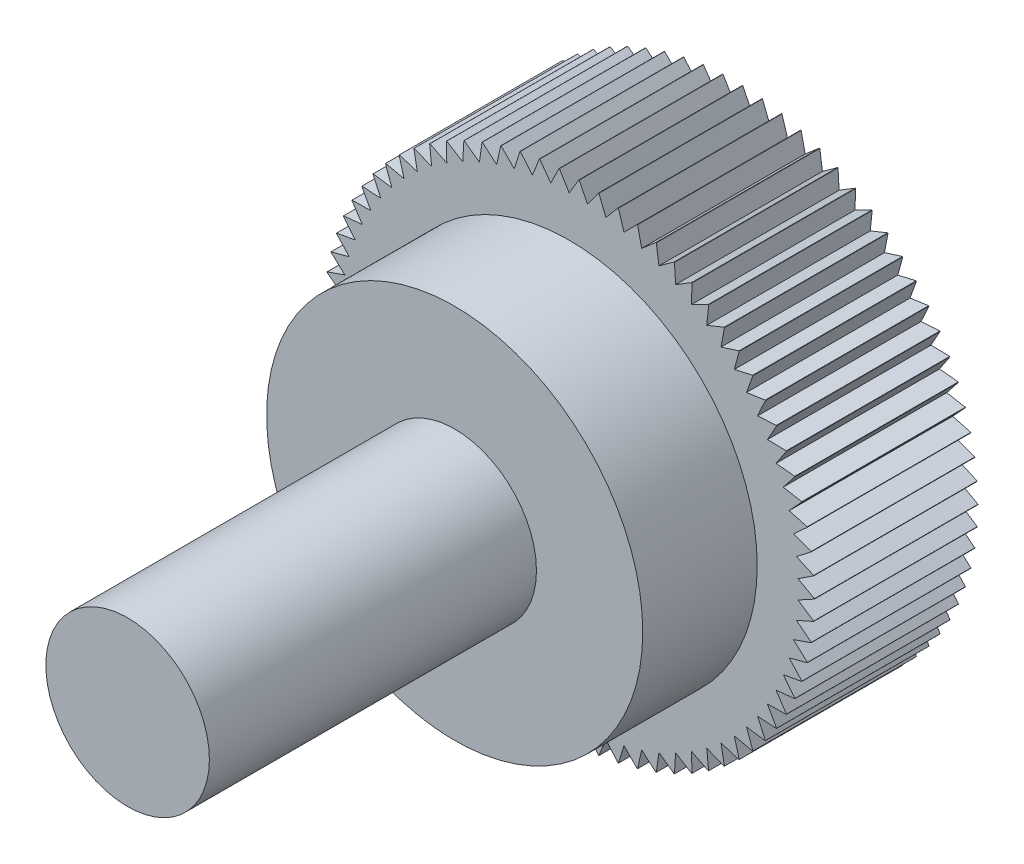
SolidWorks part; units mm, degrees
ref_plane "Front" through (0, 0, 0) normal (0, 0, 1) x (1, 0, 0)
ref_plane "Top" through (0, 0, 0) normal (0, 1, 0) x (1, 0, 0)
ref_plane "Right" through (0, 0, 0) normal (1, 0, 0) x (0, 0, -1)
sketch "Sketch1" plane through (0, 0, 0) normal (0, 0, 1) x (1, 0, 0)
  circle A0 centre (0, 0) radius 7.5
  dimension "D1" = 15
extrude "Extrude1" add sketch "Sketch1" along normal blind 5
sketch "Sketch2" plane through (0, 0, 5) normal (0, 0, 1) x (1, 0, 0)
  circle A0 centre (0, 0) radius 5.75
  dimension "D1" = 11.5
extrude "Extrude2" add sketch "Sketch2" along normal blind 3.5
sketch "Sketch3" plane through (0, 0, 8.5) normal (0, 0, 1) x (1, 0, 0)
  circle A0 centre (0, 0) radius 2.5
  dimension "D1" = 5
extrude "Extrude3" add sketch "Sketch3" along normal blind 10
sketch "Sketch4" plane through (0, 0, 0) normal (0, 0, -1) x (-1, 0, 0)
  line L0 (0, 0) -> (0, 7.5) construction
  line L1 (-0.3, 7.5) -> (0, 7)
  line L2 (0.3, 7.5) -> (0, 7)
  line L3 (-0.3, 7.5) -> (0.3, 7.5)
  line L4 (0.3045, 7.4998) -> (0.5633, 6.9773)
  line L5 (0.9025, 7.4515) -> (0.5633, 6.9773)
  line L6 (0.3045, 7.4998) -> (0.9025, 7.4515)
  line L7 (0.907, 7.451) -> (1.1229, 6.9094)
  line L8 (1.4992, 7.3548) -> (1.1229, 6.9094)
  line L9 (0.907, 7.451) -> (1.4992, 7.3548)
  line L10 (1.5036, 7.3539) -> (1.6752, 6.7966)
  line L11 (2.0862, 7.2103) -> (1.6752, 6.7966)
  line L12 (1.5036, 7.3539) -> (2.0862, 7.2103)
  line L13 (2.0904, 7.209) -> (2.2167, 6.6398)
  line L14 (2.6596, 7.019) -> (2.2167, 6.6398)
  line L15 (2.0904, 7.209) -> (2.6596, 7.019)
  line L16 (2.6638, 7.0174) -> (2.7438, 6.4399)
  line L17 (3.2157, 6.7823) -> (2.7438, 6.4399)
  line L18 (2.6638, 7.0174) -> (3.2157, 6.7823)
  line L19 (3.2198, 6.7803) -> (3.2531, 6.1982)
  line L20 (3.7511, 6.5015) -> (3.2531, 6.1982)
  line L21 (3.2198, 6.7803) -> (3.7511, 6.5015)
  line L22 (3.7549, 6.4993) -> (3.7413, 5.9163)
  line L23 (4.2621, 6.1786) -> (3.7413, 5.9163)
  line L24 (3.7549, 6.4993) -> (4.2621, 6.1786)
  line L25 (4.2657, 6.176) -> (4.2052, 5.5961)
  line L26 (4.7454, 5.8156) -> (4.2052, 5.5961)
  line L27 (4.2657, 6.176) -> (4.7454, 5.8156)
  line L28 (4.7489, 5.8128) -> (4.6419, 5.2396)
  line L29 (5.198, 5.4149) -> (4.6419, 5.2396)
  line L30 (4.7489, 5.8128) -> (5.198, 5.4149)
  line L31 (5.2012, 5.4118) -> (5.0484, 4.8491)
  line L32 (5.6168, 4.9791) -> (5.0484, 4.8491)
  line L33 (5.2012, 5.4118) -> (5.6168, 4.9791)
  line L34 (5.6198, 4.9757) -> (5.4222, 4.4271)
  line L35 (5.9993, 4.511) -> (5.4222, 4.4271)
  line L36 (5.6198, 4.9757) -> (5.9993, 4.511)
  line L37 (6.002, 4.5074) -> (5.7609, 3.9765)
  line L38 (6.3428, 4.0136) -> (5.7609, 3.9765)
  line L39 (6.002, 4.5074) -> (6.3428, 4.0136)
  line L40 (6.3452, 4.0098) -> (6.0622, 3.5)
  line L41 (6.6452, 3.4902) -> (6.0622, 3.5)
  line L42 (6.3452, 4.0098) -> (6.6452, 3.4902)
  line L43 (6.6473, 3.4862) -> (6.3242, 3.0008)
  line L44 (6.9045, 2.9442) -> (6.3242, 3.0008)
  line L45 (6.6473, 3.4862) -> (6.9045, 2.9442)
  line L46 (6.9062, 2.94) -> (6.5451, 2.4822)
  line L47 (7.119, 2.379) -> (6.5451, 2.4822)
  line L48 (6.9062, 2.94) -> (7.119, 2.379)
  line L49 (7.1204, 2.3748) -> (6.7236, 1.9475)
  line L50 (7.2874, 1.7985) -> (6.7236, 1.9475)
  line L51 (7.1204, 2.3748) -> (7.2874, 1.7985)
  line L52 (7.2884, 1.7941) -> (6.8585, 1.4002)
  line L53 (7.4084, 1.2063) -> (6.8585, 1.4002)
  line L54 (7.2884, 1.7941) -> (7.4084, 1.2063)
  line L55 (7.4092, 1.2018) -> (6.949, 0.8438)
  line L56 (7.4815, 0.6062) -> (6.949, 0.8438)
  line L57 (7.4092, 1.2018) -> (7.4815, 0.6062)
  line L58 (7.4818, 0.6018) -> (6.9943, 0.2819)
  line L59 (7.506, 0.0022) -> (6.9943, 0.2819)
  line L60 (7.4818, 0.6018) -> (7.506, 0.0022)
  line L61 (7.506, -0.0022) -> (6.9943, -0.2819)
  line L62 (7.4818, -0.6018) -> (6.9943, -0.2819)
  line L63 (7.506, -0.0022) -> (7.4818, -0.6018)
  line L64 (7.4815, -0.6062) -> (6.949, -0.8438)
  line L65 (7.4092, -1.2018) -> (6.949, -0.8438)
  line L66 (7.4815, -0.6062) -> (7.4092, -1.2018)
  line L67 (7.4084, -1.2063) -> (6.8585, -1.4002)
  line L68 (7.2884, -1.7941) -> (6.8585, -1.4002)
  line L69 (7.4084, -1.2063) -> (7.2884, -1.7941)
  line L70 (7.2874, -1.7985) -> (6.7236, -1.9475)
  line L71 (7.1204, -2.3748) -> (6.7236, -1.9475)
  line L72 (7.2874, -1.7985) -> (7.1204, -2.3748)
  line L73 (7.119, -2.379) -> (6.5451, -2.4822)
  line L74 (6.9062, -2.94) -> (6.5451, -2.4822)
  line L75 (7.119, -2.379) -> (6.9062, -2.94)
  line L76 (6.9045, -2.9442) -> (6.3242, -3.0008)
  line L77 (6.6473, -3.4862) -> (6.3242, -3.0008)
  line L78 (6.9045, -2.9442) -> (6.6473, -3.4862)
  line L79 (6.6452, -3.4902) -> (6.0622, -3.5)
  line L80 (6.3452, -4.0098) -> (6.0622, -3.5)
  line L81 (6.6452, -3.4902) -> (6.3452, -4.0098)
  line L82 (6.3428, -4.0136) -> (5.7609, -3.9765)
  line L83 (6.002, -4.5074) -> (5.7609, -3.9765)
  line L84 (6.3428, -4.0136) -> (6.002, -4.5074)
  line L85 (5.9993, -4.511) -> (5.4222, -4.4271)
  line L86 (5.6198, -4.9757) -> (5.4222, -4.4271)
  line L87 (5.9993, -4.511) -> (5.6198, -4.9757)
  line L88 (5.6168, -4.9791) -> (5.0484, -4.8491)
  line L89 (5.2012, -5.4118) -> (5.0484, -4.8491)
  line L90 (5.6168, -4.9791) -> (5.2012, -5.4118)
  line L91 (5.198, -5.4149) -> (4.6419, -5.2396)
  line L92 (4.7489, -5.8128) -> (4.6419, -5.2396)
  line L93 (5.198, -5.4149) -> (4.7489, -5.8128)
  line L94 (4.7454, -5.8156) -> (4.2052, -5.5961)
  line L95 (4.2657, -6.176) -> (4.2052, -5.5961)
  line L96 (4.7454, -5.8156) -> (4.2657, -6.176)
  line L97 (4.2621, -6.1786) -> (3.7413, -5.9163)
  line L98 (3.7549, -6.4993) -> (3.7413, -5.9163)
  line L99 (4.2621, -6.1786) -> (3.7549, -6.4993)
  line L100 (3.7511, -6.5015) -> (3.2531, -6.1982)
  line L101 (3.2198, -6.7803) -> (3.2531, -6.1982)
  line L102 (3.7511, -6.5015) -> (3.2198, -6.7803)
  line L103 (3.2157, -6.7823) -> (2.7438, -6.4399)
  line L104 (2.6638, -7.0174) -> (2.7438, -6.4399)
  line L105 (3.2157, -6.7823) -> (2.6638, -7.0174)
  line L106 (2.6596, -7.019) -> (2.2167, -6.6398)
  line L107 (2.0904, -7.209) -> (2.2167, -6.6398)
  line L108 (2.6596, -7.019) -> (2.0904, -7.209)
  line L109 (2.0862, -7.2103) -> (1.6752, -6.7966)
  line L110 (1.5036, -7.3539) -> (1.6752, -6.7966)
  line L111 (2.0862, -7.2103) -> (1.5036, -7.3539)
  line L112 (1.4992, -7.3548) -> (1.1229, -6.9094)
  line L113 (0.907, -7.451) -> (1.1229, -6.9094)
  line L114 (1.4992, -7.3548) -> (0.907, -7.451)
  line L115 (0.9025, -7.4515) -> (0.5633, -6.9773)
  line L116 (0.3045, -7.4998) -> (0.5633, -6.9773)
  line L117 (0.9025, -7.4515) -> (0.3045, -7.4998)
  line L118 (0.3, -7.5) -> (0, -7)
  line L119 (-0.3, -7.5) -> (0, -7)
  line L120 (0.3, -7.5) -> (-0.3, -7.5)
  line L121 (-0.3045, -7.4998) -> (-0.5633, -6.9773)
  line L122 (-0.9025, -7.4515) -> (-0.5633, -6.9773)
  line L123 (-0.3045, -7.4998) -> (-0.9025, -7.4515)
  line L124 (-0.907, -7.451) -> (-1.1229, -6.9094)
  line L125 (-1.4992, -7.3548) -> (-1.1229, -6.9094)
  line L126 (-0.907, -7.451) -> (-1.4992, -7.3548)
  line L127 (-1.5036, -7.3539) -> (-1.6752, -6.7966)
  line L128 (-2.0862, -7.2103) -> (-1.6752, -6.7966)
  line L129 (-1.5036, -7.3539) -> (-2.0862, -7.2103)
  line L130 (-2.0904, -7.209) -> (-2.2167, -6.6398)
  line L131 (-2.6596, -7.019) -> (-2.2167, -6.6398)
  line L132 (-2.0904, -7.209) -> (-2.6596, -7.019)
  line L133 (-2.6638, -7.0174) -> (-2.7438, -6.4399)
  line L134 (-3.2157, -6.7823) -> (-2.7438, -6.4399)
  line L135 (-2.6638, -7.0174) -> (-3.2157, -6.7823)
  line L136 (-3.2198, -6.7803) -> (-3.2531, -6.1982)
  line L137 (-3.7511, -6.5015) -> (-3.2531, -6.1982)
  line L138 (-3.2198, -6.7803) -> (-3.7511, -6.5015)
  line L139 (-3.7549, -6.4993) -> (-3.7413, -5.9163)
  line L140 (-4.2621, -6.1786) -> (-3.7413, -5.9163)
  line L141 (-3.7549, -6.4993) -> (-4.2621, -6.1786)
  line L142 (-4.2657, -6.176) -> (-4.2052, -5.5961)
  line L143 (-4.7454, -5.8156) -> (-4.2052, -5.5961)
  line L144 (-4.2657, -6.176) -> (-4.7454, -5.8156)
  line L145 (-4.7489, -5.8128) -> (-4.6419, -5.2396)
  line L146 (-5.198, -5.4149) -> (-4.6419, -5.2396)
  line L147 (-4.7489, -5.8128) -> (-5.198, -5.4149)
  line L148 (-5.2012, -5.4118) -> (-5.0484, -4.8491)
  line L149 (-5.6168, -4.9791) -> (-5.0484, -4.8491)
  line L150 (-5.2012, -5.4118) -> (-5.6168, -4.9791)
  line L151 (-5.6198, -4.9757) -> (-5.4222, -4.4271)
  line L152 (-5.9993, -4.511) -> (-5.4222, -4.4271)
  line L153 (-5.6198, -4.9757) -> (-5.9993, -4.511)
  line L154 (-6.002, -4.5074) -> (-5.7609, -3.9765)
  line L155 (-6.3428, -4.0136) -> (-5.7609, -3.9765)
  line L156 (-6.002, -4.5074) -> (-6.3428, -4.0136)
  line L157 (-6.3452, -4.0098) -> (-6.0622, -3.5)
  line L158 (-6.6452, -3.4902) -> (-6.0622, -3.5)
  line L159 (-6.3452, -4.0098) -> (-6.6452, -3.4902)
  line L160 (-6.6473, -3.4862) -> (-6.3242, -3.0008)
  line L161 (-6.9045, -2.9442) -> (-6.3242, -3.0008)
  line L162 (-6.6473, -3.4862) -> (-6.9045, -2.9442)
  line L163 (-6.9062, -2.94) -> (-6.5451, -2.4822)
  line L164 (-7.119, -2.379) -> (-6.5451, -2.4822)
  line L165 (-6.9062, -2.94) -> (-7.119, -2.379)
  line L166 (-7.1204, -2.3748) -> (-6.7236, -1.9475)
  line L167 (-7.2874, -1.7985) -> (-6.7236, -1.9475)
  line L168 (-7.1204, -2.3748) -> (-7.2874, -1.7985)
  line L169 (-7.2884, -1.7941) -> (-6.8585, -1.4002)
  line L170 (-7.4084, -1.2063) -> (-6.8585, -1.4002)
  line L171 (-7.2884, -1.7941) -> (-7.4084, -1.2063)
  line L172 (-7.4092, -1.2018) -> (-6.949, -0.8438)
  line L173 (-7.4815, -0.6062) -> (-6.949, -0.8438)
  line L174 (-7.4092, -1.2018) -> (-7.4815, -0.6062)
  line L175 (-7.4818, -0.6018) -> (-6.9943, -0.2819)
  line L176 (-7.506, -0.0022) -> (-6.9943, -0.2819)
  line L177 (-7.4818, -0.6018) -> (-7.506, -0.0022)
  line L178 (-7.506, 0.0022) -> (-6.9943, 0.2819)
  line L179 (-7.4818, 0.6018) -> (-6.9943, 0.2819)
  line L180 (-7.506, 0.0022) -> (-7.4818, 0.6018)
  line L181 (-7.4815, 0.6062) -> (-6.949, 0.8438)
  line L182 (-7.4092, 1.2018) -> (-6.949, 0.8438)
  line L183 (-7.4815, 0.6062) -> (-7.4092, 1.2018)
  line L184 (-7.4084, 1.2063) -> (-6.8585, 1.4002)
  line L185 (-7.2884, 1.7941) -> (-6.8585, 1.4002)
  line L186 (-7.4084, 1.2063) -> (-7.2884, 1.7941)
  line L187 (-7.2874, 1.7985) -> (-6.7236, 1.9475)
  line L188 (-7.1204, 2.3748) -> (-6.7236, 1.9475)
  line L189 (-7.2874, 1.7985) -> (-7.1204, 2.3748)
  line L190 (-7.119, 2.379) -> (-6.5451, 2.4822)
  line L191 (-6.9062, 2.94) -> (-6.5451, 2.4822)
  line L192 (-7.119, 2.379) -> (-6.9062, 2.94)
  line L193 (-6.9045, 2.9442) -> (-6.3242, 3.0008)
  line L194 (-6.6473, 3.4862) -> (-6.3242, 3.0008)
  line L195 (-6.9045, 2.9442) -> (-6.6473, 3.4862)
  line L196 (-6.6452, 3.4902) -> (-6.0622, 3.5)
  line L197 (-6.3452, 4.0098) -> (-6.0622, 3.5)
  line L198 (-6.6452, 3.4902) -> (-6.3452, 4.0098)
  line L199 (-6.3428, 4.0136) -> (-5.7609, 3.9765)
  line L200 (-6.002, 4.5074) -> (-5.7609, 3.9765)
  line L201 (-6.3428, 4.0136) -> (-6.002, 4.5074)
  line L202 (-5.9993, 4.511) -> (-5.4222, 4.4271)
  line L203 (-5.6198, 4.9757) -> (-5.4222, 4.4271)
  line L204 (-5.9993, 4.511) -> (-5.6198, 4.9757)
  line L205 (-5.6168, 4.9791) -> (-5.0484, 4.8491)
  line L206 (-5.2012, 5.4118) -> (-5.0484, 4.8491)
  line L207 (-5.6168, 4.9791) -> (-5.2012, 5.4118)
  line L208 (-5.198, 5.4149) -> (-4.6419, 5.2396)
  line L209 (-4.7489, 5.8128) -> (-4.6419, 5.2396)
  line L210 (-5.198, 5.4149) -> (-4.7489, 5.8128)
  line L211 (-4.7454, 5.8156) -> (-4.2052, 5.5961)
  line L212 (-4.2657, 6.176) -> (-4.2052, 5.5961)
  line L213 (-4.7454, 5.8156) -> (-4.2657, 6.176)
  line L214 (-4.2621, 6.1786) -> (-3.7413, 5.9163)
  line L215 (-3.7549, 6.4993) -> (-3.7413, 5.9163)
  line L216 (-4.2621, 6.1786) -> (-3.7549, 6.4993)
  line L217 (-3.7511, 6.5015) -> (-3.2531, 6.1982)
  line L218 (-3.2198, 6.7803) -> (-3.2531, 6.1982)
  line L219 (-3.7511, 6.5015) -> (-3.2198, 6.7803)
  line L220 (-3.2157, 6.7823) -> (-2.7438, 6.4399)
  line L221 (-2.6638, 7.0174) -> (-2.7438, 6.4399)
  line L222 (-3.2157, 6.7823) -> (-2.6638, 7.0174)
  line L223 (-2.6596, 7.019) -> (-2.2167, 6.6398)
  line L224 (-2.0904, 7.209) -> (-2.2167, 6.6398)
  line L225 (-2.6596, 7.019) -> (-2.0904, 7.209)
  line L226 (-2.0862, 7.2103) -> (-1.6752, 6.7966)
  line L227 (-1.5036, 7.3539) -> (-1.6752, 6.7966)
  line L228 (-2.0862, 7.2103) -> (-1.5036, 7.3539)
  line L229 (-1.4992, 7.3548) -> (-1.1229, 6.9094)
  line L230 (-0.907, 7.451) -> (-1.1229, 6.9094)
  line L231 (-1.4992, 7.3548) -> (-0.907, 7.451)
  line L232 (-0.9025, 7.4515) -> (-0.5633, 6.9773)
  line L233 (-0.3045, 7.4998) -> (-0.5633, 6.9773)
  line L234 (-0.9025, 7.4515) -> (-0.3045, 7.4998)
  circle A0 centre (0, 0) radius 7.5 construction
  dimension "D1" = 0.3
  dimension "D2" = 0.5
extrude "Cut-Extrude1" cut sketch "Sketch4" against normal blind 20
sketch "Sketch5" plane through (0, 0, 0) normal (0, 0, -1) x (-1, 0, 0)
  circle A0 centre (0, 0) radius 4
  dimension "D1" = 8
extrude "Cut-Extrude2" cut sketch "Sketch5" against normal blind 0.5
